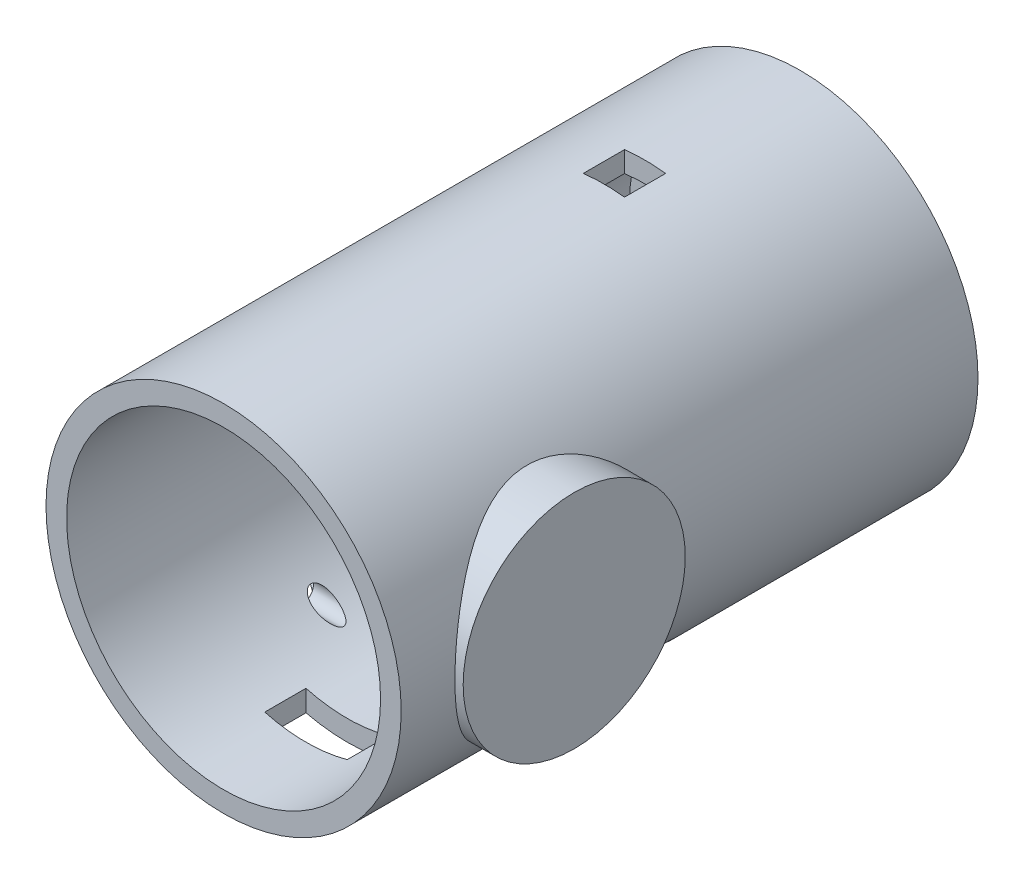
SolidWorks part; units mm, degrees
ref_plane "Front Plane" through (0, 0, 0) normal (0, 0, 1) x (1, 0, 0)
ref_plane "Top Plane" through (0, 0, 0) normal (0, 1, 0) x (1, 0, 0)
ref_plane "Right Plane" through (0, 0, 0) normal (1, 0, 0) x (0, 0, -1)
sketch "Sketch1" plane through (0, 0, 0) normal (0, 0, 1) x (1, 0, 0)
  circle A1 centre (0, 0) radius 43.1
  dimension "D1" = 86.2
extrude "Boss-Extrude1" add sketch "Sketch1" along normal blind 140
ref_plane "Plane1" through (0, 43.1, 0) normal (0, 1, 0) x (1, 0, 0)
sketch "Sketch6" plane through (0, 43.1, 0) normal (0, 1, 0) x (1, 0, 0)
  line L2 (-5, -47.7) -> (5, -47.7)
  line L3 (-5, -47.7) -> (-5, -37.7)
  line L4 (-5, -37.7) -> (5, -37.7)
  line L5 (5, -47.7) -> (5, -37.7)
  line L6 (-5, -47.7) -> (5, -37.7) construction
  line L7 (-5, -37.7) -> (5, -47.7) construction
  point P2 (0, -42.7)
  dimension "D2" = 10
  dimension "D1" = 42.7
  dimension "D3" = 10
extrude "Cut-Extrude3" cut sketch "Sketch6" against normal through all
ref_plane "Plane2" through (45.1, 0, 0) normal (1, 0, 0) x (0, 0, -1)
sketch "Sketch8" plane through (45.1, 0, 0) normal (1, 0, 0) x (0, 0, -1)
  circle A0 centre (-100, 0) radius 26.95
  dimension "D1" = 53.9
  dimension "D2" = 100
extrude "Boss-Extrude2" add sketch "Sketch8" against normal blind 20
mirror "Mirror1" [suppressed] about plane through (0, 0, 0) normal (1, 0, 0)
sketch "Sketch5" plane through (0, 0, 140) normal (0, 0, 1) x (1, 0, 0)
  circle A0 centre (0, 0) radius 31.75
  dimension "D1" = 63.5
sketch "Sketch2" plane through (0, 0, 140) normal (0, 0, 1) x (1, 0, 0)
  circle A0 centre (0, 0) radius 38.1
  dimension "D1" = 76.2
extrude "Cut-Extrude4" cut sketch "Sketch5" against normal through all
extrude "Cut-Extrude5" cut sketch "Sketch2" against normal blind 135
sketch "Sketch9" plane through (0, 0, 5) normal (0, 0, 1) x (1, 0, 0)
  circle A0 centre (0, 0) radius 38.1
  circle A1 centre (0, 0) radius 36.44
  dimension "D1" = 76.2
  dimension "D2" = 1.66
extrude "Boss-Extrude3" add sketch "Sketch9" along normal blind 10
sketch "Sketch10" plane through (0, 0, 0) normal (0, 1, 0) x (1, 0, 0)
  line L0 (43.1, 0) -> (-43.1, 0) construction
  line L1 (-10, -120) -> (10, -120)
  line L2 (-10, -120) -> (-10, -110)
  line L3 (-10, -110) -> (10, -110)
  line L4 (10, -120) -> (10, -110)
  line L5 (-10, -120) -> (10, -110) construction
  line L6 (-10, -110) -> (10, -120) construction
  point P0 (0, -115)
  point P7 (-10, -115)
  point P8 (0, 0)
  dimension "D1" = 110
  dimension "D2" = 10
  dimension "D3" = 20
extrude "Cut-Extrude6" cut sketch "Sketch10" against normal through all
sketch "Sketch11" plane through (0, 0, 0) normal (1, 0, 0) x (0, 0, -1)
  circle A0 centre (-64.7, -32) radius 2.5
  circle A1 centre (-94.7, -32) radius 2.5
  point P5 (0, 0)
  dimension "D3" = 5
  dimension "D1" = 64.7
  dimension "D2" = 32
  dimension "D4" = 30
extrude "Cut-Extrude7" cut sketch "Sketch11" against normal through all both and the other way through all
ref_plane "Plane3" through (26, 0, 0) normal (1, 0, 0) x (0, 0, -1)
ref_plane "Plane4" through (-26, 0, 0) normal (1, 0, 0) x (0, 0, -1)
sketch "Sketch12" plane through (26, 0, 0) normal (1, 0, 0) x (0, 0, -1)
  circle A0 centre (-64.7, -32) radius 3.5
  circle A1 centre (-94.7, -32) radius 3.5
  dimension "D1" = 7
extrude "Cut-Extrude8" cut sketch "Sketch12" along normal through all
sketch "Sketch13" plane through (-26, 0, 0) normal (1, 0, 0) x (0, 0, -1)
  line L0 (-92.6793, -28.5) -> (-96.7207, -28.5)
  line L1 (-62.6793, -28.5) -> (-60.6585, -32)
  line L2 (-60.6585, -32) -> (-62.6793, -35.5)
  line L3 (-62.6793, -35.5) -> (-66.7207, -35.5)
  line L4 (-66.7207, -35.5) -> (-68.7415, -32)
  line L5 (-68.7415, -32) -> (-66.7207, -28.5)
  line L6 (-66.7207, -28.5) -> (-62.6793, -28.5)
  line L7 (-96.7207, -28.5) -> (-98.7415, -32)
  line L8 (-98.7415, -32) -> (-96.7207, -35.5)
  line L9 (-96.7207, -35.5) -> (-92.6793, -35.5)
  line L10 (-92.6793, -35.5) -> (-90.6585, -32)
  line L11 (-90.6585, -32) -> (-92.6793, -28.5)
  circle A0 centre (-94.7, -32) radius 3.5 construction
  circle A1 centre (-64.7, -32) radius 3.5 construction
  dimension "D1" = 7
extrude "Cut-Extrude9" cut sketch "Sketch13" against normal through all
